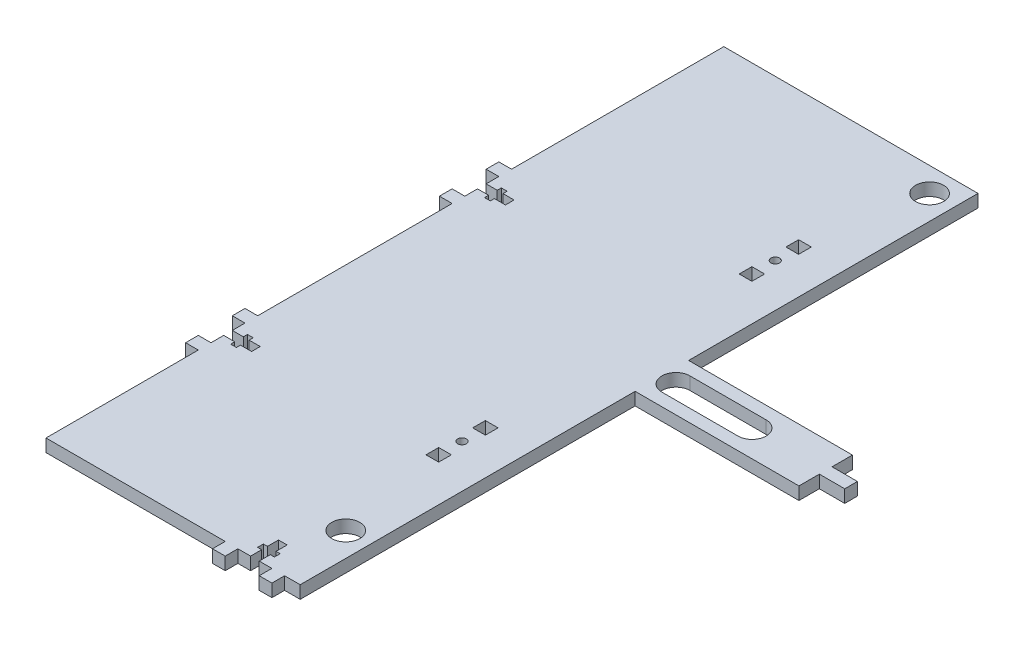
SolidWorks part; units mm, degrees
ref_plane "Front Plane" through (0, 0, 0) normal (0, 0, 1) x (1, 0, 0)
ref_plane "Top Plane" through (0, 0, 0) normal (0, 1, 0) x (1, 0, 0)
ref_plane "Right Plane" through (0, 0, 0) normal (1, 0, 0) x (0, 0, -1)
sketch "Axle Support Plate" plane through (0, 0, 0) normal (0, 1, 0) x (1, 0, 0)
  line L0 (51.4759, 157.4574) -> (51.4759, -134.6426) construction
  line L1 (38.7759, 169.5676) -> (38.7759, -103.4054) construction
  line L4 (63.5861, -169.5676) -> (63.5861, -1.9727)
  line L5 (-63.5861, 169.5676) -> (63.5861, -169.5676) construction
  line L6 (-63.5861, -169.5676) -> (63.5861, 169.5676) construction
  line L7 (-63.5861, -63.6496) -> (-63.5861, 33.6324)
  line L8 (-63.5861, 169.5676) -> (63.5861, 169.5676)
  line L9 (0, 169.5676) -> (0, -169.5676) construction
  line L17 (63.5861, 11.4074) -> (2.0059, 11.4074) construction
  line L23 (55.7939, -169.5676) -> (63.5861, -169.5676)
  line L37 (63.5861, 24.7876) -> (145.5462, 24.7876)
  line L38 (145.5462, 24.7876) -> (145.5462, 14.5824)
  line L39 (145.5462, -1.9727) -> (63.5861, -1.9727)
  line L40 (70.6162, 11.4074) -> (108.7162, 11.4074) construction
  line L41 (70.6162, 18.4376) -> (108.7162, 18.4376)
  line L42 (70.6162, 4.3773) -> (108.7162, 4.3773)
  line L43 (145.5462, 8.2324) -> (158.2462, 8.2324)
  line L44 (158.2462, 8.2324) -> (158.2462, 14.5824)
  line L45 (158.2462, 14.5824) -> (145.5462, 14.5824)
  line L46 (63.5861, 24.7876) -> (63.5861, 169.5676)
  line L47 (63.5861, 24.7876) -> (63.5861, -1.9727) construction
  line L48 (63.5861, 11.4074) -> (158.2462, 11.4074) construction
  line L51 (145.5462, 8.2324) -> (145.5462, -1.9727)
  line L81 (-63.5861, 63.3504) -> (-63.5861, 169.5676)
  line L90 (26.0759, -169.5676) -> (-63.5861, -169.5676)
  line L94 (-63.5861, -169.5676) -> (-63.5861, -93.3676)
  circle A0 centre (51.4759, 157.4574) radius 7.0301
  circle A1 centre (51.4759, -134.6426) radius 7.0301
  arc A4 (70.6162, 18.4376) -> (70.6162, 4.3773) centre (70.6162, 11.4074) ccw
  arc A5 (108.7162, 4.3773) -> (108.7162, 18.4376) centre (108.7162, 11.4074) ccw
  point P8 (0, 0)
  point P15 (51.4759, 11.4074)
  point P57 (89.6662, 11.4074)
  line B0 (-63.5861, -69.9996) -> (-69.9361, -69.9996)
  line B1 (-69.9361, -69.9996) -> (-69.9361, -63.6496)
  line B2 (-69.9361, -63.6496) -> (-63.5861, -63.6496)
  line B3 (-63.5861, -76.3496) -> (-58.0511, -76.3496)
  line B4 (-58.0511, -76.3496) -> (-58.0511, -74.3086)
  line B5 (-58.0511, -74.3086) -> (-55.1511, -74.3086)
  line B6 (-55.1511, -74.3086) -> (-55.1511, -76.3496)
  line B7 (-55.1511, -76.3496) -> (-49.6161, -76.3496)
  line B8 (-49.6161, -76.3496) -> (-49.6161, -80.6676)
  line B9 (-49.6161, -80.6676) -> (-55.1511, -80.6676)
  line B10 (-55.1511, -80.6676) -> (-55.1511, -82.7086)
  line B11 (-55.1511, -82.7086) -> (-58.0511, -82.7086)
  line B12 (-58.0511, -82.7086) -> (-58.0511, -80.6676)
  line B13 (-58.0511, -80.6676) -> (-63.5861, -80.6676)
  line B14 (-49.6161, -78.5086) -> (-63.5861, -78.5086) construction
  line B15 (-63.5861, -87.0176) -> (-63.5861, -80.6676)
  line B16 (-69.9361, -93.3676) -> (-63.5861, -93.3676)
  line B17 (-63.5861, -69.9996) -> (-63.5861, -76.3496)
  line B18 (-69.9361, -87.0176) -> (-69.9361, -93.3676)
  line B19 (-63.5861, -87.0176) -> (-69.9361, -87.0176)
  line B20 (-63.5861, 57.0004) -> (-69.9361, 57.0004)
  line B21 (-69.9361, 57.0004) -> (-69.9361, 63.3504)
  line B22 (-69.9361, 63.3504) -> (-63.5861, 63.3504)
  line B23 (-63.5861, 50.6504) -> (-58.0511, 50.6504)
  line B24 (-58.0511, 50.6504) -> (-58.0511, 52.6914)
  line B25 (-58.0511, 52.6914) -> (-55.1511, 52.6914)
  line B26 (-55.1511, 52.6914) -> (-55.1511, 50.6504)
  line B27 (-55.1511, 50.6504) -> (-49.6161, 50.6504)
  line B28 (-49.6161, 50.6504) -> (-49.6161, 46.3324)
  line B29 (-49.6161, 46.3324) -> (-55.1511, 46.3324)
  line B30 (-55.1511, 46.3324) -> (-55.1511, 44.2914)
  line B31 (-55.1511, 44.2914) -> (-58.0511, 44.2914)
  line B32 (-58.0511, 44.2914) -> (-58.0511, 46.3324)
  line B33 (-58.0511, 46.3324) -> (-63.5861, 46.3324)
  line B34 (-49.6161, 48.4914) -> (-63.5861, 48.4914) construction
  line B35 (-63.5861, 39.9824) -> (-63.5861, 46.3324)
  line B36 (-69.9361, 33.6324) -> (-63.5861, 33.6324)
  line B37 (-63.5861, 57.0004) -> (-63.5861, 50.6504)
  line B38 (-69.9361, 39.9824) -> (-69.9361, 33.6324)
  line B39 (-63.5861, 39.9824) -> (-69.9361, 39.9824)
  line B40 (32.4259, -169.5676) -> (32.4259, -175.9176)
  line B41 (32.4259, -175.9176) -> (26.0759, -175.9176)
  line B42 (26.0759, -175.9176) -> (26.0759, -169.5676)
  line B43 (38.7759, -169.5676) -> (38.7759, -164.0326)
  line B44 (38.7759, -164.0326) -> (36.7349, -164.0326)
  line B45 (36.7349, -164.0326) -> (36.7349, -161.1326)
  line B46 (36.7349, -161.1326) -> (38.7759, -161.1326)
  line B47 (38.7759, -161.1326) -> (38.7759, -155.5976)
  line B48 (38.7759, -155.5976) -> (43.0939, -155.5976)
  line B49 (43.0939, -155.5976) -> (43.0939, -161.1326)
  line B50 (43.0939, -161.1326) -> (45.1349, -161.1326)
  line B51 (45.1349, -161.1326) -> (45.1349, -164.0326)
  line B52 (45.1349, -164.0326) -> (43.0939, -164.0326)
  line B53 (43.0939, -164.0326) -> (43.0939, -169.5676)
  line B54 (40.9349, -155.5976) -> (40.9349, -169.5676) construction
  line B55 (49.4439, -169.5676) -> (43.0939, -169.5676)
  line B56 (55.7939, -175.9176) -> (55.7939, -169.5676)
  line B57 (32.4259, -169.5676) -> (38.7759, -169.5676)
  line B58 (49.4439, -175.9176) -> (55.7939, -175.9176)
  line B59 (49.4439, -169.5676) -> (49.4439, -175.9176)
  line B60 (41.9509, 74.9074) -> (41.9509, 104.6254) construction
  line B61 (39.7919, 89.7664) -> (44.1099, 89.7664) construction
  line B62 (38.7759, 98.2754) -> (45.1259, 98.2754)
  line B63 (38.7759, 98.2754) -> (38.7759, 104.6254)
  line B64 (38.7759, 104.6254) -> (45.1259, 104.6254)
  line B65 (45.1259, 98.2754) -> (45.1259, 104.6254)
  line B66 (38.7759, 98.2754) -> (45.1259, 104.6254) construction
  line B67 (38.7759, 104.6254) -> (45.1259, 98.2754) construction
  line B68 (38.7759, 74.9074) -> (45.1259, 81.2574) construction
  line B69 (38.7759, 81.2574) -> (45.1259, 74.9074) construction
  line B70 (45.1259, 81.2574) -> (45.1259, 74.9074)
  line B71 (38.7759, 74.9074) -> (45.1259, 74.9074)
  line B72 (38.7759, 81.2574) -> (38.7759, 74.9074)
  line B73 (38.7759, 81.2574) -> (45.1259, 81.2574)
  circle B74 centre (41.9509, 89.7664) radius 2.159
  line B75 (41.9509, -52.0926) -> (41.9509, -81.8106) construction
  line B76 (39.7919, -66.9516) -> (44.1099, -66.9516) construction
  line B77 (38.7759, -75.4606) -> (45.1259, -75.4606)
  line B78 (38.7759, -75.4606) -> (38.7759, -81.8106)
  line B79 (38.7759, -81.8106) -> (45.1259, -81.8106)
  line B80 (45.1259, -75.4606) -> (45.1259, -81.8106)
  line B81 (38.7759, -75.4606) -> (45.1259, -81.8106) construction
  line B82 (38.7759, -81.8106) -> (45.1259, -75.4606) construction
  line B83 (38.7759, -52.0926) -> (45.1259, -58.4426) construction
  line B84 (38.7759, -58.4426) -> (45.1259, -52.0926) construction
  line B85 (45.1259, -58.4426) -> (45.1259, -52.0926)
  line B86 (38.7759, -52.0926) -> (45.1259, -52.0926)
  line B87 (38.7759, -58.4426) -> (38.7759, -52.0926)
  line B88 (38.7759, -58.4426) -> (45.1259, -58.4426)
  circle B89 centre (41.9509, -66.9516) radius 2.159
  dimension "D1" = 5.08
  dimension "D4" = 14.0603
  dimension "D5" = 5.08
  dimension "D14" = 14.0603
  dimension "D22" = 7.0301
  dimension "D25" = 36.83
  dimension "D2" = 292.1
  dimension "D6" = 12.7
  dimension "D7" = 63.5
  dimension "D9" = 89.662
  dimension "D13" = 34.925
  dimension "D23" = 6.35
  dimension "D24" = 38.1
  dimension "D26" = 12.7
  dimension "D27" = 6.35
  dimension "D29" = 76.2
  dimension "D30" = 203.2
sketch_block_instance "Male T-slot assembly-1"
sketch_block "Male T-slot assembly" parameters "D1"=6.35, "D2"=6.35, "D3"=4.318, "D4"=2.9, "D5"=8.4, "D6"=13.97, "D7"=6.35
sketch_block_instance "Male T-slot assembly-2"
sketch_block_instance "Male T-slot assembly-4"
sketch_block_instance "Female T-Slot Assembly-1"
sketch_block "Female T-Slot Assembly" parameters "D4"=4.318, "D1"=6.35, "D2"=6.35, "D3"=6.35
sketch_block_instance "Female T-Slot Assembly-3"
extrude "Boss-Extrude1" add sketch "Axle Support Plate" along normal blind 6.35 contours L23 L4 L39 L51 L43 L44 L45 L38 L37 L46 L8 region at (3.4679, 0, -0.2235)
equation "\"Ball Diameter\"= 1.75in"
equation "\"Sheet Thickness\"= 0.25in"
equation "\"Screw Diameter\"= .17in"
equation "\"Robot Diameter\"= 14in"
equation "\"Castor Screw Diameter\"= 0.22in"
equation "\"Wheel Diameter\" = 4in"
equation "\"Nut Diameter\" = 8.4mm"
equation "\"Nut Height\" = 2.9mm"
equation "\"Screw Height\" = 0.55in"
equation "\"Pulley Diameter\" = 1in"
equation "\"Reactor Height\" = 14in"
equation "\"Elevator Height\" = 11.5in"
equation "\"Elevator Width\" = \"Ball Diameter\" + 0.25in"
equation "\"D1@Boss-Extrude1\"=\"Sheet Thickness\""
equation "\"Elevator Bearing Diameter\" = sqr(2*(\"Sheet Thickness\"^2)) + 0.2in"
equation "\"Elevator Axle Length\" = \"Elevator Width\" + 8*\"Sheet Thickness\""
equation "\"D4@Axle Support Plate\"=\"Elevator Bearing Diameter\""
equation "\"D6@Axle Support Plate\"=(\"Pulley Diameter\")/2"
equation "\"D13@Axle Support Plate\"=2.5in - \"Sheet Thickness\" - (\"Ball Diameter\")/2"
equation "\"D9@Axle Support Plate\"=\"Elevator Clearance from Axis\" + \"Sheet Thickness\""
equation "\"D14@Axle Support Plate\" = \"Elevator Bearing Diameter\""
equation "\"D22@Axle Support Plate\"=\"Elevator Bearing Diameter\"/2"
equation "\"D23@Axle Support Plate\" = \"Sheet Thickness\""
equation "\"Elevator Axle Endcap Diameter\" = \"Pulley Diameter\" + 0.25in"
equation "\"D25@Axle Support Plate\"=\"Elevator Axle Endcap Diameter\"+0.2in"
equation "\"D27@Axle Support Plate\"=\"Sheet Thickness\""
equation "\"Elevator Clearance from Axis\" = 3.28in"
